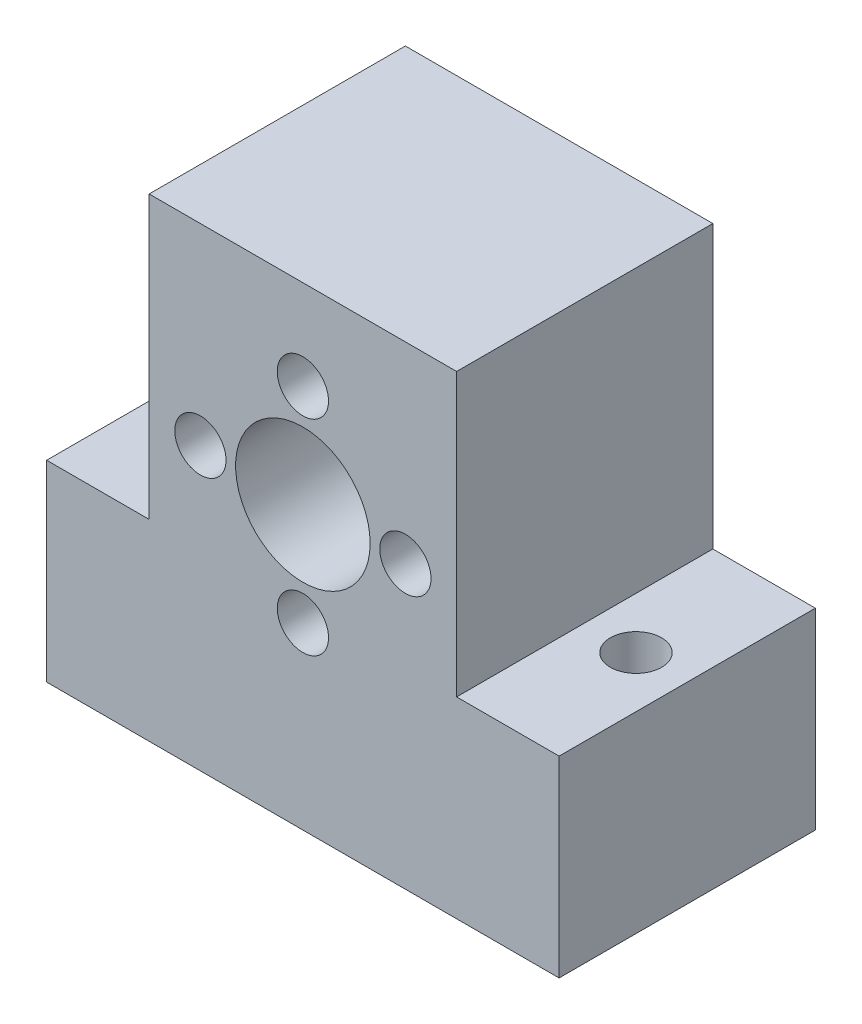
SolidWorks part; units mm, degrees
ref_plane "Front Plane" through (0, 0, 0) normal (0, 0, 1) x (1, 0, 0)
ref_plane "Top Plane" through (0, 0, 0) normal (0, 1, 0) x (1, 0, 0)
ref_plane "Right Plane" through (0, 0, 0) normal (1, 0, 0) x (0, 0, -1)
sketch "Sketch1" plane through (0, 0, 0) normal (0, 0, 1) x (1, 0, 0)
  line L0 (0, -438.3722) -> (0, 21480.2356) construction
  line L1 (-438.3722, 0) -> (21480.2356, 0) construction
  line L3 (-20, -22) -> (20, -22)
  line L4 (-20, -22) -> (-20, 15)
  line L5 (-20, 15) -> (20, 15)
  line L6 (20, -22) -> (20, 15)
  circle A0 centre (0, 0) radius 5.25
  circle A1 centre (0, 0) radius 8 construction
  circle A2 centre (0, 8) radius 2
  circle A3 centre (8, 0) radius 2
  circle A4 centre (0, -8) radius 2
  circle A5 centre (-8, 0) radius 2
  point P4 (0, 0)
  point P24 (0, 0)
  dimension "D2" = 10.5
  dimension "D4" = 16
  dimension "D5" = 4
  dimension "D7" = 8
  dimension "D8" = 8
  dimension "D1" = 15
  dimension "D3" = 40
  dimension "D9" = 22
  dimension "D10" = 20
  dimension "D6" = 4
extrude "Boss-Extrude1" add sketch "Sketch1" along normal blind 20
sketch "Sketch2" plane through (0, 15, 0) normal (0, 1, 0) x (1, 0, 0)
  line L0 (0, -1000) -> (0, 49000) construction
  line L1 (-1030, -10) -> (48970, -10) construction
  line L2 (-20, -20) -> (-20, 0) construction
  circle A0 centre (-16, -10) radius 2
  circle A1 centre (16, -10) radius 2
  point P8 (-20, -10)
  dimension "D2" = 4
  dimension "D1" = 4
extrude "Cut-Extrude1" cut sketch "Sketch2" against normal through all
sketch "Sketch3" plane through (0, 0, 0) normal (0, 0, -1) x (-1, 0, 0)
  line L0 (0, -1000) -> (0, 49000) construction
  line L1 (-1000, 0) -> (49000, 0) construction
  line L2 (-20, 15) -> (20, 15) construction
  line L3 (20, -22) -> (12, -22)
  line L4 (20, -22) -> (20, 15)
  line L5 (20, 15) -> (12, 15)
  line L6 (12, -22) -> (12, 15)
  line L7 (20, -7) -> (12, -7)
  line L8 (-20, -7) -> (-12, -7)
  line L9 (-12, -22) -> (-12, 15)
  line L10 (-20, 15) -> (-12, 15)
  line L11 (-20, -22) -> (-20, 15)
  line L12 (-20, -22) -> (-12, -22)
  line M7 (-20, 15) -> (-20, -22)
  line M10 (20, 15) -> (-20, 15)
  dimension "D1" = 12
  dimension "D2" = 15
extrude "Cut-Extrude2" cut sketch "Sketch3" against normal through all contours L7 L4 L6 M10 | L8 L9 M10 M7 region at (16, 4, 0) region at (-16, 4, 0)
